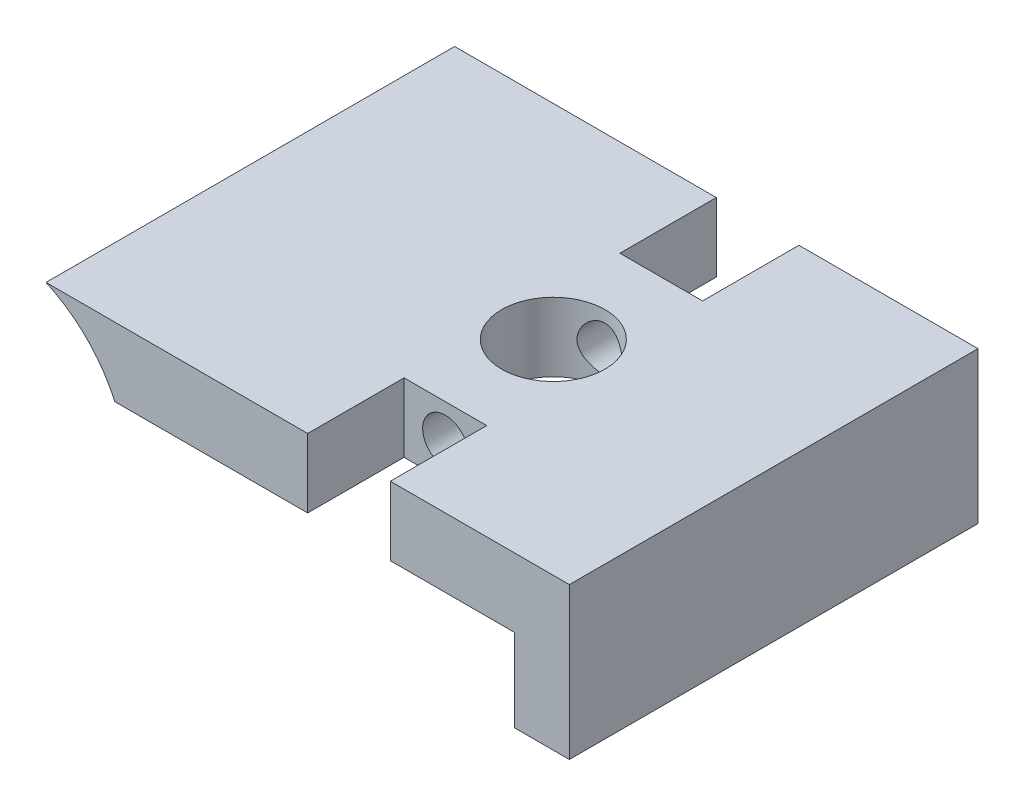
SolidWorks part; units mm, degrees
ref_plane "Front Plane" through (0, 0, 0) normal (0, 0, 1) x (1, 0, 0)
ref_plane "Top Plane" through (0, 0, 0) normal (0, 1, 0) x (1, 0, 0)
ref_plane "Right Plane" through (0, 0, 0) normal (1, 0, 0) x (0, 0, -1)
sketch "Sketch3" plane through (0, 0, 0) normal (0, 0, 1) x (1, 0, 0)
  line L0 (-19, 2.5) -> (-14, -2.5) construction
  line L1 (-14, -2.5) -> (19, -2.5)
  line L3 (-19, 2.5) -> (19, 2.5)
  line L4 (19, -2.5) -> (19, 2.5)
  line L5 (-14.5814, -1.9186) -> (19, 2.5) construction
  line L6 (-19, 2.5) -> (19, -2.5) construction
  arc A0 (-19, 2.5) -> (-14, -2.5) centre (-23.1144, -6.6144) cw
  point P0 (0, 0)
  point P6 (0, 2.5)
  dimension "D3" = 10
  dimension "D1" = 38
  dimension "D2" = 135
  dimension "D4" = 5
extrude "Boss-Extrude1" add sketch "Sketch3" along normal mid plane 29.67
sketch "Sketch4" plane through (0, 0, 14.835) normal (0, 0, 1) x (1, 0, 0)
  line L0 (19, -2.5) -> (19, 2.5) construction
  line L1 (19, 2.5) -> (-19, 2.5) construction
  line L2 (6, -2.5) -> (0, -2.5)
  line L3 (6, -2.5) -> (6, 2.5)
  line L4 (6, 2.5) -> (0, 2.5)
  line L5 (0, -2.5) -> (0, 2.5)
  line L6 (6, -2.5) -> (0, 2.5) construction
  line L7 (6, 2.5) -> (0, -2.5) construction
  circle A2 centre (3, 0) radius 1.65
  point P0 (19, 0)
  dimension "D1" = 3.3
  dimension "D5" = 16
extrude "Cut-Extrude1" cut sketch "Sketch4" against normal up to next contours A2 region at (3, 0, 14.835)
extrude "Cut-Extrude3" cut sketch "Sketch4<3>" against normal blind 7
sketch "Sketch4<3>" plane through (0, 0, 14.835) normal (0, 0, 1) x (1, 0, 0) same geometry as "Sketch4"
mirror "Mirror1" about plane through (0, 0, 0) normal (0, 0, 1) of "Cut-Extrude3"
sketch "Sketch5" plane through (0, 2.5, 0) normal (0, 1, 0) x (1, 0, 0)
  line L0 (19, -14.835) -> (19, 14.835) construction
  circle A0 centre (3, 0) radius 3.75
  point P7 (19, 0)
  dimension "D2" = 7.5
  dimension "D1" = 16
extrude "Cut-Extrude2" cut sketch "Sketch5" against normal up to next
sketch "Sketch6" plane through (0, 0, 14.835) normal (0, 0, 1) x (1, 0, 0)
  line L0 (19, -2.5) -> (19, -8.5)
  line L1 (19, -8.5) -> (15, -8.5)
  line L2 (15, -8.5) -> (15, -2.5)
  line L3 (6, -2.5) -> (19, -2.5) construction
  line L4 (15, -2.5) -> (19, -2.5)
  dimension "D1" = 6
  dimension "D2" = 4
extrude "Boss-Extrude2" add sketch "Sketch6" against normal up to surface (29.67 mm away) up to face at (12.5, 0, -14.835)
